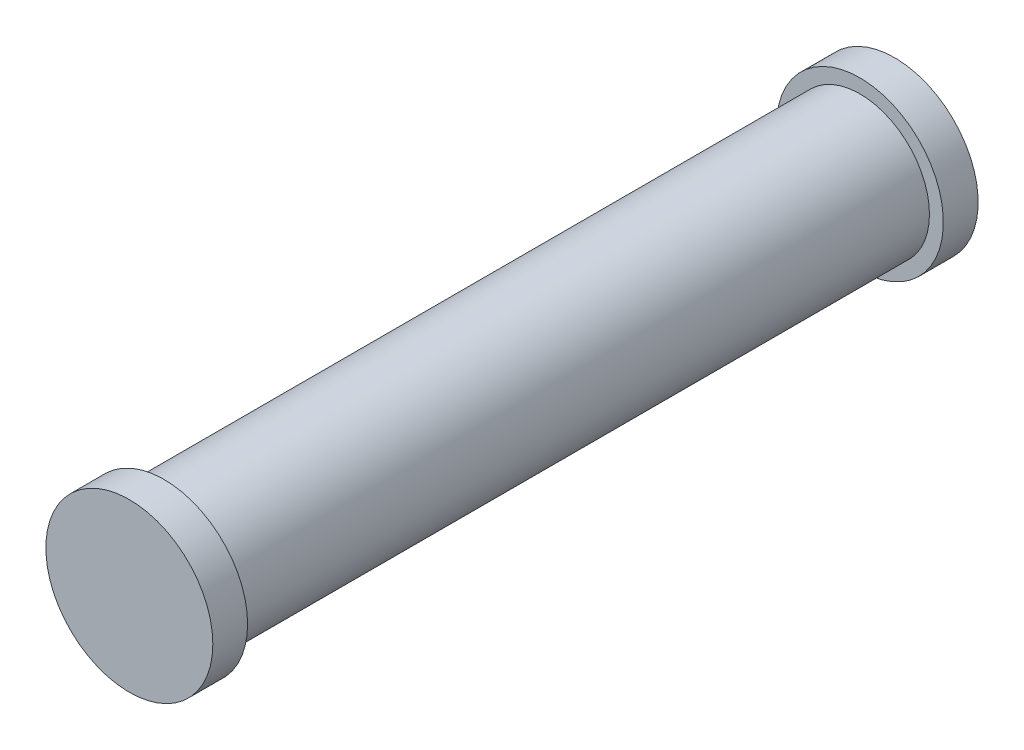
SolidWorks part; units mm, degrees
ref_plane "Alzado" through (0, 0, 0) normal (0, 0, 1) x (1, 0, 0)
ref_plane "Planta" through (0, 0, 0) normal (0, 1, 0) x (1, 0, 0)
ref_plane "Vista lateral" through (0, 0, 0) normal (1, 0, 0) x (0, 0, -1)
sketch "Croquis1" plane through (0, 0, 0) normal (0, 0, 1) x (1, 0, 0)
  circle A0 centre (0, 0) radius 0.5
  dimension "D1" = 1
extrude "Saliente-Extruir1" add sketch "Croquis1" along normal blind 5
sketch "Croquis2" plane through (0, 0, 5) normal (0, 0, 1) x (1, 0, 0)
  circle A0 centre (0, 0) radius 0.6
  dimension "D1" = 1.2
extrude "Saliente-Extruir2" add sketch "Croquis2" along normal blind 0.25
sketch "Croquis3" plane through (0, 0, 0) normal (0, 0, -1) x (-1, 0, 0)
  circle A0 centre (0, 0) radius 0.6
  dimension "D1" = 1.2
extrude "Saliente-Extruir3" add sketch "Croquis3" along normal blind 0.25 contours A0
ref_axis "Eje2" through (0, 0, 5.3858) along (0, 0, -1)
